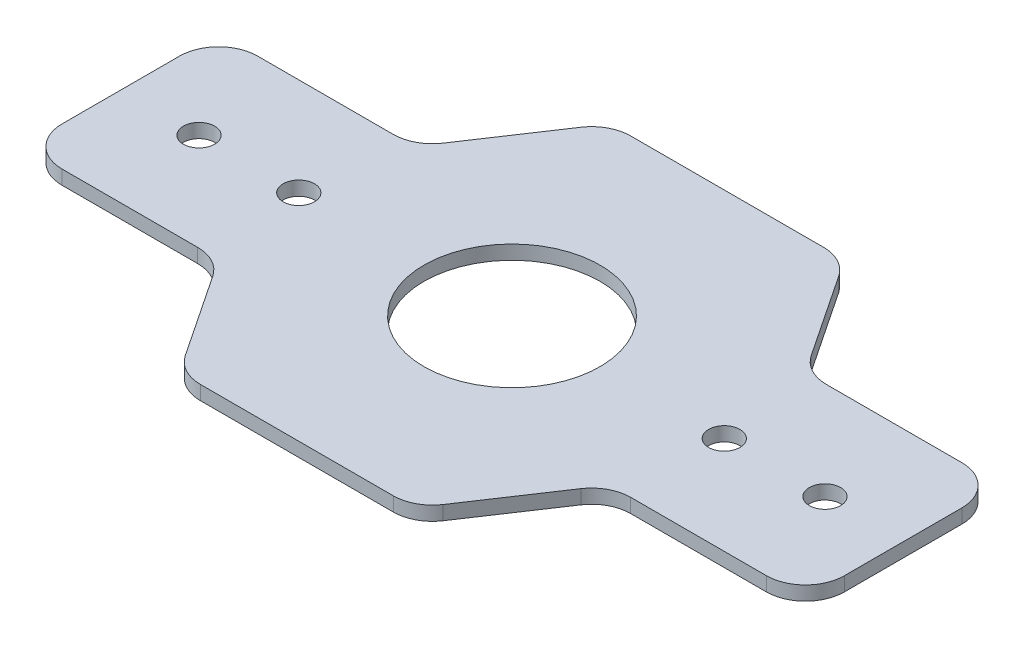
SolidWorks part; units mm, degrees
ref_plane "Front Plane" through (0, 0, 0) normal (0, 0, 1) x (1, 0, 0)
ref_plane "Top Plane" through (0, 0, 0) normal (0, 1, 0) x (1, 0, 0)
ref_plane "Right Plane" through (0, 0, 0) normal (1, 0, 0) x (0, 0, -1)
sketch "Sketch1" plane through (0, 0, 0) normal (0, 1, 0) x (1, 0, 0)
  line L0 (16.2686, 0) -> (85.3314, 0) construction
  line L1 (50.8, 0) -> (50.8, 3.1391) construction
  line L2 (19.05, 15.875) -> (31.75, 34.925)
  line L3 (-12.7, 15.875) -> (19.05, 15.875)
  line L4 (-12.7, 15.875) -> (-12.7, -15.875)
  line L5 (-12.7, -15.875) -> (19.05, -15.875)
  line L6 (114.3, 15.875) -> (114.3, -15.875)
  line L7 (-12.7, 15.875) -> (114.3, -15.875) construction
  line L8 (-12.7, -15.875) -> (114.3, 15.875) construction
  line L9 (31.75, 34.925) -> (69.85, 34.925)
  line L10 (69.85, 34.925) -> (82.55, 15.875)
  line L11 (50.8, 34.925) -> (50.8, 29.0511) construction
  line L12 (69.85, -34.925) -> (82.55, -15.875)
  line L13 (31.75, -34.925) -> (69.85, -34.925)
  line L14 (19.05, -15.875) -> (31.75, -34.925)
  line L15 (82.55, -15.875) -> (114.3, -15.875)
  line L16 (82.55, 15.875) -> (114.3, 15.875)
  circle A0 centre (0, 0) radius 2.54
  circle A1 centre (101.6, 0) radius 2.54
  circle A2 centre (16.2686, 0) radius 2.54 construction
  circle A3 centre (85.3314, 0) radius 2.54 construction
  dimension "D1" = 5.08
  dimension "D3" = 127
  dimension "D4" = 31.75
  dimension "D5" = 69.0628
  dimension "D2" = 101.6
  dimension "D6" = 19.05
  dimension "D7" = 31.75
  dimension "D8" = 38.1
extrude "Boss-Extrude1" add sketch "Sketch1" along normal blind 2.286
fillet "Fillet1" radius 6.35 12 edges at (19.05, 1.143, -15.875) (31.75, 1.143, -34.925) (69.85, 1.143, -34.925) (82.55, 1.143, -15.875) (114.3, 1.143, -15.875) (114.3, 1.143, 15.875) (82.55, 1.143, 15.875) (69.85, 1.143, 34.925) (31.75, 1.143, 34.925) (19.05, 1.143, 15.875) (-12.7, 1.143, -15.875) (-12.7, 1.143, 15.875)
sketch "Sketch2" plane through (0, 2.286, 0) normal (0, 1, 0) x (1, 0, 0)
  circle A0 centre (50.8, 0) radius 14.2875
  circle A1 centre (0, 0) radius 2.54 construction
  dimension "D1" = 50.8
  dimension "D2" = 28.575
extrude "Cut-Extrude1" cut sketch "Sketch2" against normal blind 3.175
sketch "Sketch3" plane through (0, 2.286, 0) normal (0, 1, 0) x (1, 0, 0)
  circle A2 centre (85.2557, 0) radius 2.54
  circle A3 centre (16.1929, 0) radius 2.54
  circle A4 centre (101.6, 0) radius 2.54 construction
  dimension "D1" = 69.0628
  dimension "D2" = 5.08
  dimension "D3" = 5.08
  dimension "D4" = 16.3443
extrude "Cut-Extrude2" cut sketch "Sketch3" against normal through all
